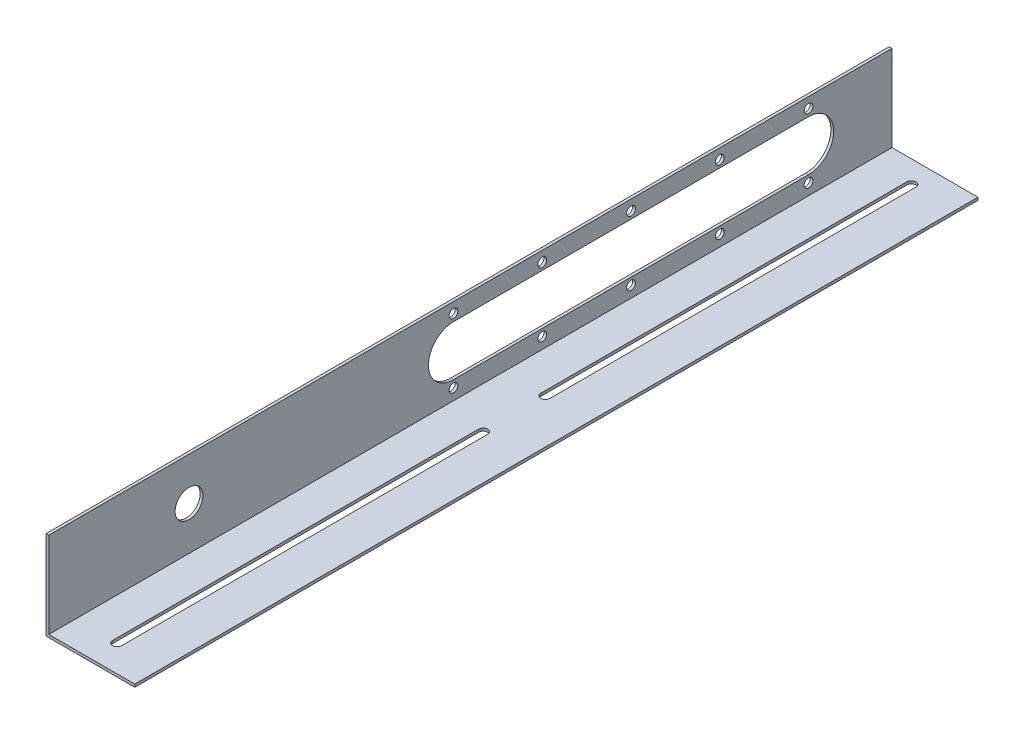
SolidWorks part; units mm, degrees
material "6061 Alloy"
ref_plane "Front Plane" through (0, 0, 0) normal (0, 0, 1) x (1, 0, 0)
ref_plane "Top Plane" through (0, 0, 0) normal (0, 1, 0) x (1, 0, 0)
ref_plane "Right Plane" through (0, 0, 0) normal (1, 0, 0) x (0, 0, -1)
sketch "Sketch3" plane through (0, 0, 0) normal (0, 0, 1) x (1, 0, 0)
  line L0 (0, 0) -> (0, 49.2125)
  line L1 (0, 49.2125) -> (-1.5875, 49.2125)
  line L2 (-1.5875, 49.2125) -> (-1.5875, -1.5875)
  line L3 (-1.5875, -1.5875) -> (49.2125, -1.5875)
  line L4 (49.2125, -1.5875) -> (49.2125, 0)
  line L5 (49.2125, 0) -> (0, 0)
  dimension "D1" = 1.5875
  dimension "D2" = 1.5875
  dimension "D3" = 50.8
  dimension "D4" = 50.8
extrude "Boss-Extrude2" add sketch "Sketch3" along normal blind 431.8
sketch "Sketch6" plane through (0, 0, 0) normal (1, 0, 0) x (0, 0, -1)
  line L0 (-250.952, 24.8285) -> (-47.752, 24.8285) construction
  line L1 (-250.952, 39.1795) -> (-47.752, 39.1795)
  line L2 (-250.952, 10.4775) -> (-47.752, 10.4775)
  line L4 (0, 0) -> (0, 49.2125) construction
  line L5 (-431.8, 49.2125) -> (0, 49.2125) construction
  arc A0 (-250.952, 39.1795) -> (-250.952, 10.4775) centre (-250.952, 24.8285) ccw
  arc A1 (-47.752, 10.4775) -> (-47.752, 39.1795) centre (-47.752, 24.8285) ccw
  point P2 (-149.352, 24.8285)
  dimension "D3" = 47.752
  dimension "D1" = 28.702
  dimension "D2" = 203.2
  dimension "D4" = 24.384
extrude "Cut-Extrude3" cut sketch "Sketch6" against normal blind 127
sketch "Sketch7" plane through (0, 0, 0) normal (1, 0, 0) x (0, 0, -1)
  line L1 (-431.8, 49.2125) -> (0, 49.2125) construction
  line L2 (0, 0) -> (0, 49.2125) construction
  circle A0 centre (-402.336, 24.7736) radius 7.9629
  dimension "D1" = 15.9258
  dimension "D3" = 24.4389
  dimension "D4" = 402.336
extrude "Cut-Extrude4" cut sketch "Sketch7" against normal through all
sketch "Sketch8" plane through (0, 0, 0) normal (1, 0, 0) x (0, 0, -1)
  line L2 (-47.752, 43.2435) -> (-250.952, 43.2435)
  line L3 (-47.752, 43.2435) -> (-250.952, 43.2435) construction
  line L4 (-250.952, 43.2435) -> (-149.352, 43.2435) construction
  line L5 (-250.952, 6.4135) -> (-47.752, 6.4135)
  line L6 (-250.952, 6.4135) -> (-47.752, 6.4135) construction
  line L7 (-149.352, 43.2435) -> (-47.752, 43.2435) construction
  line L8 (-250.952, 6.4135) -> (-149.352, 6.4135) construction
  line L9 (-149.352, 6.4135) -> (-47.752, 6.4135) construction
  point P0 (-149.352, 6.4135)
  point P1 (-250.952, 43.2435)
  point P6 (-250.952, 6.4135)
  point P7 (-149.352, 43.2435)
  point P8 (-200.152, 43.2435)
  point P9 (-47.752, 43.2435)
  point P10 (-47.752, 6.4135)
  point P13 (-98.552, 43.2435)
  point P14 (-200.152, 6.4135)
  point P15 (-98.552, 6.4135)
  dimension "D1" = 4.064
  dimension "D2" = 4.064
hole_wizard "#10 (0.1935) Diameter Hole1" positions "Sketch9" profile "Sketch10" hole size "#10" standard "ANSI Inch" end condition through all
sketch "Sketch9" plane through (0, 0, 0) normal (1, 0, 0) x (0, 0, -1)
  point P0 (-250.952, 43.2435)
  point P3 (-200.152, 43.2435)
  point P6 (-149.352, 43.2435)
  point P9 (-98.552, 43.2435)
  point P12 (-47.752, 43.2435)
  point P15 (-47.752, 6.4135)
  point P18 (-98.552, 6.4135)
  point P21 (-149.352, 6.4135)
  point P24 (-200.152, 6.4135)
  point P27 (-250.952, 6.4135)
sketch "Sketch10" plane through (0, 43.2435, 250.952) normal (0, 1, 0) x (0, 0, -1)
  line L0 (0, 0) -> (0, 1.5875)
  line L1 (0, 1.5875) -> (2.5, 1.5875)
  line L2 (2.5, 1.5875) -> (2.5, 0)
  line L5 (2.5, 0) -> (0, 0)
  line L11 (0, -6.35) -> (0, 107.95) construction
  dimension "Thru Hole Dia." = 5
  dimension "Thru Hole Depth" = 1.5875
sketch "Sketch13" plane through (0, 0, 431.8) normal (0, 0, 1) x (1, 0, 0)
  point P0 (-1.5875, -1.5875)
  line M1 (49.2125, 0) -> (0, 0)
  line M2 (0, 0) -> (0, 49.2125)
  line M3 (0, 49.2125) -> (-1.5875, 49.2125)
  line M4 (-1.5875, 49.2125) -> (-1.5875, -1.5875)
  line M5 (-1.5875, -1.5875) -> (49.2125, -1.5875)
  line M6 (49.2125, -1.5875) -> (49.2125, 0)
extrude "Boss-Extrude3" add sketch "Sketch13" along normal blind 50.8 contours M6 M1 M2 M3 M4 M5 region at (48.4941, -0.7937, 431.8)
sketch "Sketch14" plane through (0, -1.5875, 0) normal (0, -1, 0) x (1, 0, 0)
  line L0 (23.8125, 12.7) -> (23.8125, 222.25) construction
  line L1 (21.2328, 12.7) -> (21.2328, 222.25)
  line L2 (26.3922, 12.7) -> (26.3922, 222.25)
  line L3 (23.8125, 257.7703) -> (23.8125, 467.3203) construction
  line L4 (21.2328, 257.7703) -> (21.2328, 467.3203)
  line L5 (26.3922, 257.7703) -> (26.3922, 467.3203)
  line L6 (-1.5875, 0) -> (49.2125, 0) construction
  line L7 (-1.5875, 482.6) -> (49.2125, 482.6) construction
  arc A0 (21.2328, 12.7) -> (26.3922, 12.7) centre (23.8125, 12.7) ccw
  arc A1 (26.3922, 222.25) -> (21.2328, 222.25) centre (23.8125, 222.25) ccw
  arc A2 (21.2328, 257.7703) -> (26.3922, 257.7703) centre (23.8125, 257.7703) ccw
  arc A3 (26.3922, 467.3203) -> (21.2328, 467.3203) centre (23.8125, 467.3203) ccw
  point P2 (23.8125, 117.475)
  point P8 (23.8125, 362.5453)
  point P16 (23.8125, 469.9)
  dimension "D1" = 12.7
  dimension "D2" = 12.7
  dimension "D4" = 209.55
  dimension "D5" = 5.1594
extrude "Cut-Extrude5" cut sketch "Sketch14" against normal through all
